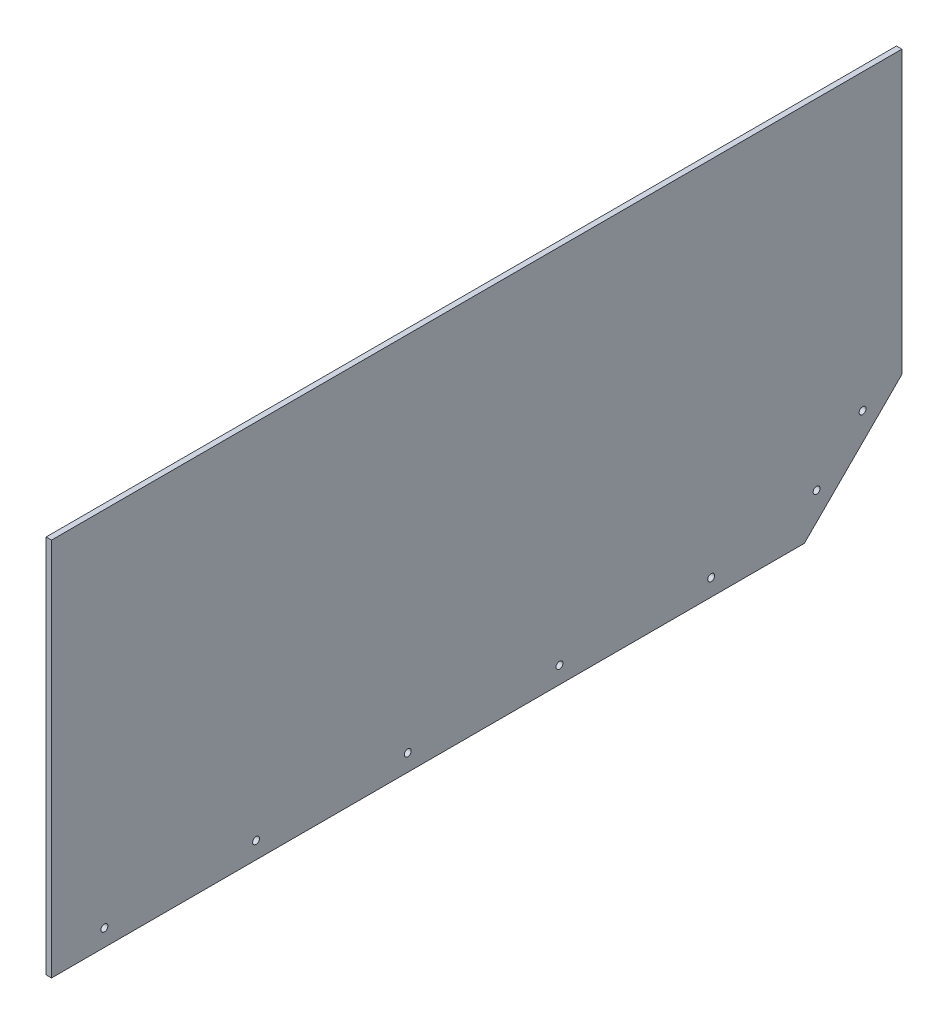
SolidWorks part; units mm, degrees
material "6061-T6 (SS)"
ref_plane "X-Y Datum" through (0, 0, 0) normal (0, 0, 1) x (1, 0, 0)
ref_plane "X-Z Datum" through (0, 0, 0) normal (0, 1, 0) x (1, 0, 0)
ref_plane "Y-Z Datum" through (0, 0, 0) normal (1, 0, 0) x (0, 0, -1)
sketch "Sketch1" plane through (0, 0, 0) normal (1, 0, 0) x (0, 0, -1)
  line L1 (-249.174, 82.55) -> (249.174, 82.55)
  line L2 (-249.174, 82.55) -> (-249.174, -82.55)
  line L3 (-249.174, -82.55) -> (249.174, -82.55)
  line L4 (249.174, 82.55) -> (249.174, -82.55)
  line L5 (-249.174, 82.55) -> (249.174, -82.55) construction
  line L6 (-249.174, -82.55) -> (249.174, 82.55) construction
  point P0 (0, 0)
  dimension "D1" = 165.1
  dimension "D2" = 498.348
extrude "Boss-Extrude1" add sketch "Sketch1" along normal mid plane 3.175
sketch "Sketch2" plane through (1.5875, 0, 0) normal (1, 0, 0) x (0, 0, -1)
  line L3 (192.024, -139.7) -> (-249.174, -139.7)
  line L5 (-249.174, -82.55) -> (249.174, -82.55) construction
  line L6 (-249.174, -82.55) -> (249.174, -82.55)
  line L7 (-249.174, -82.55) -> (-249.174, -139.7)
  line L12 (192.024, -139.7) -> (249.174, -82.55)
  line M10 (-249.174, -82.55) -> (249.174, -82.55)
  dimension "D1" = 45
  dimension "D5" = 57.15
extrude "Boss-Extrude2" add sketch "Sketch2" against normal blind 3.175 contours L3 L12 M10 region at (1.5875, -110.5456, 13.9978)
sketch "Sketch3" plane through (1.5875, 0, 0) normal (1, 0, 0) x (0, 0, -1)
  line L0 (-218.186, -139.7) -> (-218.186, -129.794)
  line L1 (192.024, -139.7) -> (-249.174, -139.7) construction
  line L2 (-218.186, -129.794) -> (-249.174, -129.794)
  line L3 (-249.174, 82.55) -> (-249.174, -139.7) construction
  circle A0 centre (-218.186, -129.794) radius 2.025
  dimension "D1" = 30.988
  dimension "D2" = 9.906
extrude "Cut-Extrude1" cut sketch "Sketch3" against normal blind 3.175 contours L2 A0 L0 | L0 A0 L2 region at (1.5875, -130.6534, 219.0454) region at (1.5875, -129.5075, 217.8995)
pattern_linear "LPattern1" count 5 spacing 88.9 along (0, 0, -1) of "Cut-Extrude1"
sketch "Sketch4" plane through (1.5875, 0, 0) normal (1, 0, 0) x (0, 0, -1)
  line L0 (192.024, -139.7) -> (183.9418, -131.6178)
  line L1 (183.9418, -131.6178) -> (199.2082, -116.3513)
  circle A0 centre (199.2082, -116.3513) radius 2.025
extrude "Cut-Extrude2" cut sketch "Sketch4" against normal through all contours A0 region at (1.5875, -118.1693, -199.9612)
pattern_linear "LPattern2" count 2 spacing 38.1 along (0, 0.7071, -0.7071) of "Cut-Extrude2"
